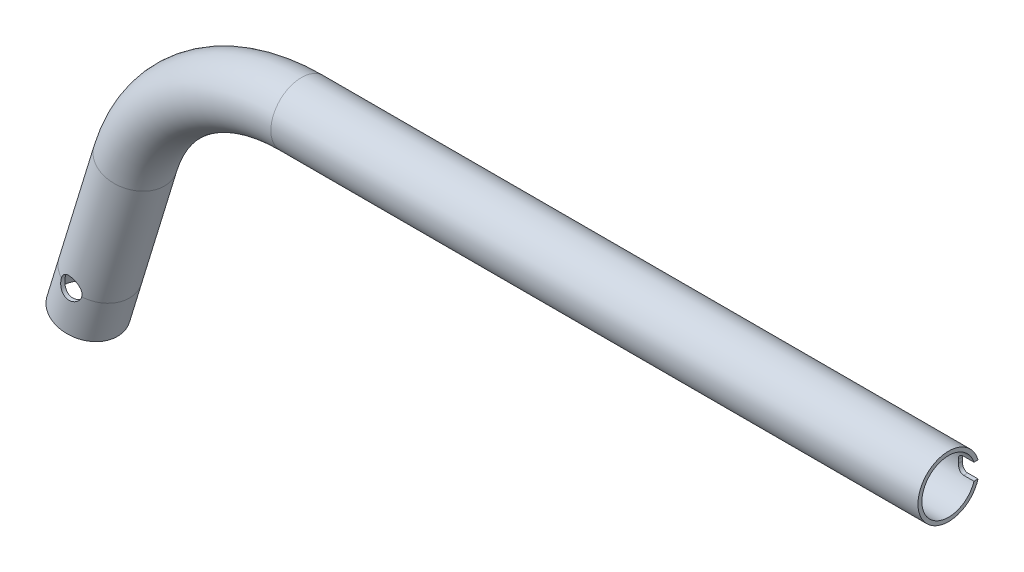
SolidWorks part; units mm, degrees
ref_plane "Front Plane" through (0, 0, 0) normal (0, 0, 1) x (1, 0, 0)
ref_plane "Top Plane" through (0, 0, 0) normal (0, 1, 0) x (1, 0, 0)
ref_plane "Right Plane" through (0, 0, 0) normal (1, 0, 0) x (0, 0, -1)
sketch "Sketch1" plane through (0, 0, 0) normal (0, 0, 1) x (1, 0, 0)
  line L0 (-92.2396, 0) -> (92.2396, 0)
  line L1 (-143.88, -38.2119) -> (-154.7604, -73.8)
  line L2 (92.2396, 0) -> (108.8396, 0)
  line L3 (-154.7604, -73.8) -> (-158.4903, -86)
  arc A0 (-92.2396, 0) -> (-143.88, -38.2119) centre (-92.2396, -54) ccw
  point P4 (0, 0)
  point P10 (-154.7604, -73.8)
  dimension "D2" = 54
  dimension "D1" = 73
  dimension "D3" = 73.8
  dimension "D4" = 247
  dimension "D5" = 86
  dimension "D6" = 73
  dimension "D7" = 16.6
ref_plane "Plane1" through (92.2396, 0, 0) normal (1, 0, 0) x (0, 0, -1)
sketch "Sketch3" plane through (92.2396, 0, 0) normal (1, 0, 0) x (0, 0, -1)
  circle A0 centre (0, 0) radius 9.5
  circle A1 centre (0, 0) radius 8.3
  dimension "D1" = 1.2
  dimension "D2" = 19
sweep "Sweep2" add profiles "Sketch3" path "Sketch1"
ref_axis "Axis1" through (108.8396, 0, 0) along (-1, 0, 0)
ref_axis "Axis2" through (-142.3269, -33.1317, 0) along (-0.2924, -0.9563, 0)
sketch "Sketch4" plane through (0, 0, 0) normal (0, 0, 1) x (1, 0, 0)
  line L0 (-163.8453, -71.0225) -> (-145.6755, -76.5775) construction
  line L1 (92.2396, -101.4635) -> (92.2396, 101.4635) construction
  line L2 (108.8396, 0) -> (92.2396, 0) construction
  line L3 (108.8396, -9.5) -> (108.8396, 9.5) construction
  line L4 (108.8396, 0) -> (-92.2396, 0) construction
  line L5 (108.8396, 2.5555) -> (108.8396, -2.5555)
  line L6 (90.2396, -5.5) -> (94.2396, -5.5)
  line L7 (88.2396, -3.5) -> (88.2396, 3.5)
  line L8 (90.2396, 5.5) -> (94.2396, 5.5)
  line L9 (96.2396, -3.5) -> (96.2396, 3.5)
  line L10 (88.2396, -5.5) -> (96.2396, 5.5) construction
  line L11 (88.2396, 5.5) -> (96.2396, -5.5) construction
  line L12 (105.6396, -2.5555) -> (108.8396, -2.5555)
  line L13 (103.6396, -0.5555) -> (103.6396, 0.5555)
  line L14 (105.6396, 2.5555) -> (108.8396, 2.5555)
  line L16 (103.6396, -2.5555) -> (108.8396, 0) construction
  line L17 (103.6396, 2.5555) -> (108.8396, 0) construction
  circle A0 centre (-154.7604, -73.8) radius 3.3
  arc A1 (90.2396, -5.5) -> (88.2396, -3.5) centre (90.2396, -3.5) cw
  arc A2 (96.2396, -3.5) -> (94.2396, -5.5) centre (94.2396, -3.5) cw
  arc A3 (94.2396, 5.5) -> (96.2396, 3.5) centre (94.2396, 3.5) cw
  arc A4 (90.2396, 5.5) -> (88.2396, 3.5) centre (90.2396, 3.5) ccw
  arc A5 (105.6396, -2.5555) -> (103.6396, -0.5555) centre (105.6396, -0.5555) cw
  arc A6 (103.6396, 0.5555) -> (105.6396, 2.5555) centre (105.6396, 0.5555) cw
  dimension "D1" = 16.6
  dimension "D4" = 2
  dimension "D5" = 2
  dimension "D2" = 8
  dimension "D3" = 11
extrude "Cut-Extrude1" cut sketch "Sketch4" against normal up to next
sketch "Sketch5" plane through (0, 0, 0) normal (0, 0, 1) x (1, 0, 0)
  circle A0 centre (-154.7604, -73.8) radius 3.3
extrude "Cut-Extrude2" cut sketch "Sketch5" along normal through all
